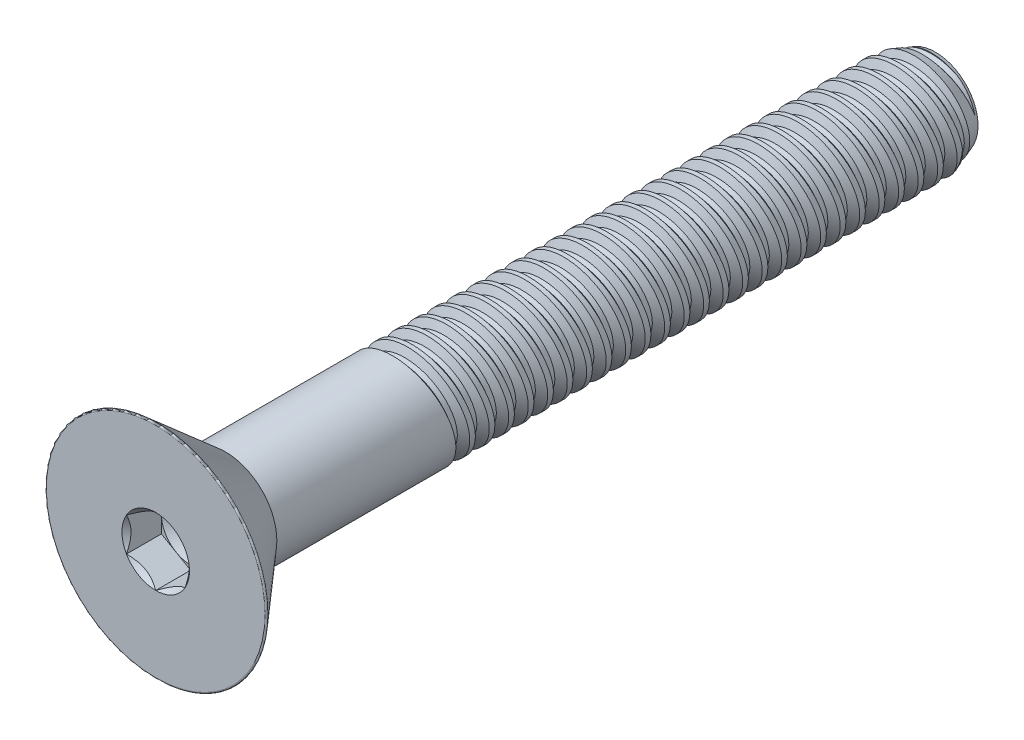
SolidWorks part; units mm, degrees
material "AISI 4340 Steel, normalized"
ref_plane "Front" through (0, 0, 0) normal (0, 0, 1) x (1, 0, 0)
ref_plane "Top" through (0, 0, 0) normal (0, 1, 0) x (1, 0, 0)
ref_plane "Right" through (0, 0, 0) normal (1, 0, 0) x (0, 0, -1)
sketch "Sketch1" plane through (0, 0, 0) normal (1, 0, 0) x (0, 0, -1)
  line L0 (0, 0) -> (-2.8448, 0) construction
  line L1 (0, 0) -> (28.9052, 0)
  line L2 (0, 0) -> (0, 2.0828)
  line L3 (0, 2.0828) -> (28.9052, 2.0828)
  line L4 (28.9052, 0) -> (28.9052, 2.0828)
  line L5 (0, -2.0828) -> (28.9052, -2.0828) construction
  dimension "Thread Dia" = 4.1656
  dimension "Length" = 31.75
  dimension "Head Height" = 2.8448
revolve "Revolve1" add sketch "Sketch1" angle 360 about L0
ref_plane "Plane1" through (0, 0, 2.8448) normal (0, 0, 1) x (1, 0, 0)
sketch "Sketch2" plane through (0, 0, 0) normal (1, 0, 0) x (0, 0, -1)
  line L0 (6.6802, 2.0828) -> (6.6802, -2.0828) construction
  line L1 (6.6802, -2.0828) -> (7.474, -2.0828) construction
  line L2 (7.474, -2.0828) -> (6.6802, 2.0828) construction
  line L3 (6.6802, 2.0828) -> (6.7777, 2.1014) construction
  line L4 (6.7777, 2.1014) -> (7.4599, 2.2314)
  line L5 (7.4599, 2.2314) -> (7.2967, 1.7629)
  line L6 (7.2967, 1.7629) -> (7.1017, 1.7258)
  line L7 (7.1017, 1.7258) -> (6.7777, 2.1014)
  line L8 (7.1992, 1.7443) -> (7.1188, 2.1664) construction
  line L9 (0, -2.0828) -> (28.9052, -2.0828) construction
  line L10 (0, 2.0828) -> (28.9052, 2.0828) construction
  line L11 (28.9052, 0) -> (28.9052, 2.0828) construction
  line L12 (7.1347, 2.0828) -> (7.9285, -2.0828) construction
  line L13 (6.6802, -0.1622) -> (8.383, 0.1622) construction
  line L14 (-269.5448, 2.0828) -> (-269.5448, -2.0828) construction
  point P19 (7.5316, 0)
  dimension "D1" = 60
  dimension "Thread Pitch" = 0.7937
  dimension "D2" = 0.0992
  dimension "D3" = 0.1984
  dimension "D4" = 0.7937
  dimension "Thread Length" = 298.45
  dimension "Min Thread Length" = 22.225
revolve "Cut-Revolve1" cut sketch "Sketch2" angle 360 about L13
sketch "Sketch3" plane through (0, 0, 0) normal (1, 0, 0) x (0, 0, -1)
  line L0 (28.9052, 1.7258) -> (27.9243, 2.0828)
  line L1 (27.9243, 2.0828) -> (28.9052, 2.0828)
  line L2 (28.9052, 2.0828) -> (28.9052, 1.7258)
  line L3 (0, 2.0828) -> (28.9052, 2.0828) construction
  line L4 (28.9052, 0) -> (28.9052, 2.0828) construction
  line L5 (27.9243, 0) -> (0, 0) construction
  line L6 (27.9243, 2.0828) -> (27.9243, -2.0828) construction
  line L7 (0, -2.0828) -> (28.9052, -2.0828) construction
  dimension "D1" = 20
  dimension "D2" = 4.1656
revolve "Cut-Revolve2" cut sketch "Sketch3" angle 360 about L5
pattern_linear "LPattern1" count 28 spacing 0.7937 along (0, 0, 1)
sketch "Sketch4" plane through (0, 0, 0) normal (0, 0, 1) x (1, 0, 0)
  circle A0 centre (0, 0) radius 4.5593
  dimension "Head Dia" = 9.1186
extrude "Extrude1" add sketch "Sketch4" along normal up to surface (2.8448 mm away)
sketch "Sketch9" plane through (0, 0, 0) normal (1, 0, 0) x (0, 0, -1)
  line L0 (-2.8448, 4.5593) -> (0, 2.0864)
  line L1 (0, 2.0864) -> (0, 4.5593)
  line L2 (0, 4.5593) -> (-2.8448, 4.5593)
  line L3 (0, 0) -> (-2.8448, 0) construction
  line L6 (-2.8448, -4.5593) -> (0, -2.0864) construction
  line L7 (0, -4.5593) -> (0, 4.5593) construction
  line L8 (-2.8448, 4.5593) -> (-2.8448, -4.5593) construction
  line L9 (0, 4.5593) -> (-2.8448, 4.5593) construction
  dimension "D1" = 82
revolve "Cut-Revolve3" cut sketch "Sketch9" angle 360 about L3
fillet "Fillet1" radius 0.0508
sketch "Sketch6" plane through (0, 0, 2.8448) normal (0, 0, 1) x (1, 0, 0)
  line L1 (0, -1.3748) -> (1.1906, -0.6874)
  line L2 (1.1906, -0.6874) -> (1.1906, 0.6874)
  line L3 (1.1906, 0.6874) -> (0, 1.3748)
  line L4 (0, 1.3748) -> (-1.1906, 0.6874)
  line L5 (-1.1906, 0.6874) -> (-1.1906, -0.6874)
  line L6 (-1.1906, -0.6874) -> (0, -1.3748)
  circle A0 centre (0, 0) radius 1.1906 construction
  dimension "Hex" = 2.3813
extrude "Cut-Extrude1" cut sketch "Sketch6" against normal blind 1.4224
sketch "Sketch7" plane through (0, 0, 2.8448) normal (0, 0, 1) x (1, 0, 0)
  circle A0 centre (0, 0) radius 1.3748
extrude "Cut-Extrude4" cut sketch "Sketch7" against normal blind 1.4224 draft 45
sketch "Sketch8" plane through (0, 0, 1.4224) normal (0, 0, 1) x (1, 0, 0)
  circle A0 centre (0, 0) radius 1.1906 construction
  circle A1 centre (0, 0) radius 1.1906
extrude "Cut-Extrude5" cut sketch "Sketch8" against normal blind 0.4741 draft 60
equation "\"D2@Sketch2\"=\"Thread Pitch@Sketch2\"/8"
equation "\"D3@Sketch2\"=\"Thread Pitch@Sketch2\"/4"
equation "\"D4@Sketch2\"=\"Thread Pitch@Sketch2\""
equation "\"D3@LPattern1\"=\"Thread Pitch@Sketch2\""
equation "\"D1@LPattern1\"=\"Min Thread Length@Sketch2\"/\"Thread Pitch@Sketch2\""
equation "\"D1@Cut-Extrude1\"=\"Head Height@Sketch1\"/2"
equation "\"D1@Cut-Extrude4\"=\"D1@Cut-Extrude1\""
equation "\"D1@Cut-Extrude5\"=\"D1@Cut-Extrude1\"/3"
